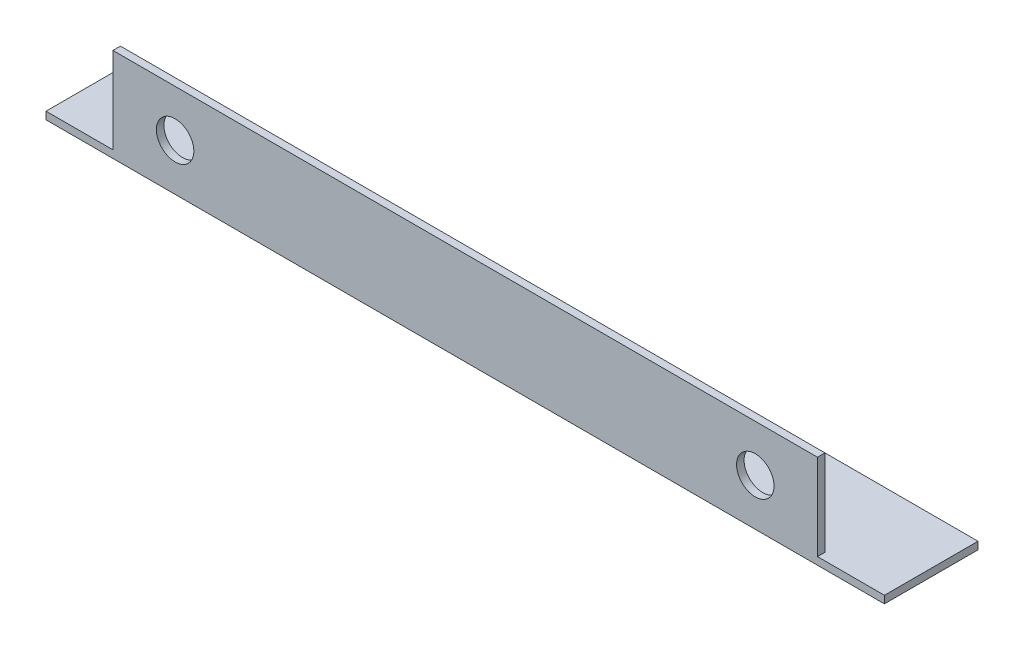
SolidWorks part; units mm, degrees
ref_plane "Спереди" through (0, 0, 0) normal (0, 0, 1) x (1, 0, 0)
ref_plane "Сверху" through (0, 0, 0) normal (0, 1, 0) x (1, 0, 0)
ref_plane "Справа" through (0, 0, 0) normal (1, 0, 0) x (0, 0, -1)
sketch "Эскиз1" plane through (0, 0, 0) normal (1, 0, 0) x (0, 0, -1)
  line L0 (0, 25) -> (0, 0)
  line L1 (0, 0) -> (25, 0)
extrude "Вытянуть-Тонкостенный1" add sketch "Эскиз1" along normal blind 224 thin thin type one direction reverse wall 2
sketch "Эскиз2" plane through (0, 0, 0) normal (0, 0, 1) x (1, 0, 0)
  line L0 (112, 0) -> (112, -9.5468) construction
  line L1 (224, 0) -> (0, 0) construction
  line L2 (206.1166, 25) -> (206.1166, 2)
  line L3 (0, 25) -> (17.8834, 25)
  line L4 (0, 25) -> (0, 2)
  line L5 (0, 2) -> (17.8834, 2)
  line L6 (17.8834, 25) -> (17.8834, 2)
  line L7 (224, 2) -> (206.1166, 2)
  line L8 (224, 25) -> (224, 2)
  line L9 (224, 25) -> (206.1166, 25)
  circle A0 centre (34.5, 12.5) radius 5
  circle A1 centre (189.5, 12.5) radius 5
  dimension "D1" = 77.5
extrude "Вырез-Вытянуть1" cut sketch "Эскиз2" against normal through all
